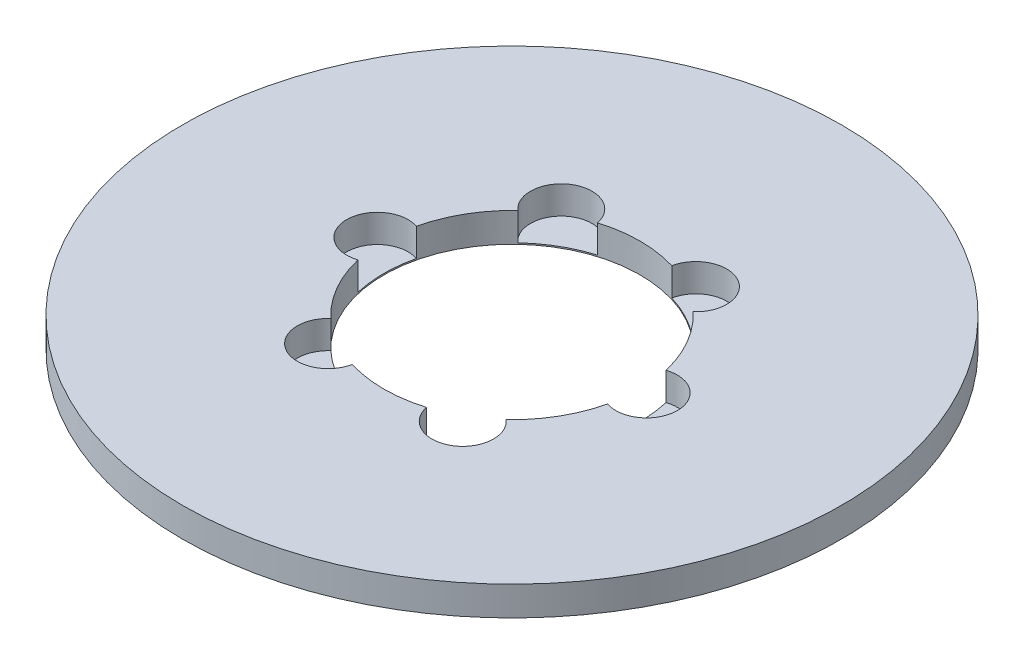
SolidWorks part; units mm, degrees
ref_plane "Front Plane" through (0, 0, 0) normal (0, 0, 1) x (1, 0, 0)
ref_plane "Top Plane" through (0, 0, 0) normal (0, 1, 0) x (1, 0, 0)
ref_plane "Right Plane" through (0, 0, 0) normal (1, 0, 0) x (0, 0, -1)
sketch "Sketch1" plane through (0, 0, 0) normal (0, 1, 0) x (1, 0, 0)
  circle A0 centre (0, 0) radius 45
  dimension "FLANGE_OD" = 90
extrude "Boss-Extrude1" add sketch "Sketch1" along normal blind 4
sketch "Sketch2" plane through (0, 0, 0) normal (0, 1, 0) x (1, 0, 0)
  circle A0 centre (0, 0) radius 17.5
  dimension "BORE_D" = 35
extrude "Cut-Extrude1" cut sketch "Sketch2" along normal through all
sketch "Sketch3" plane through (0, 4, 0) normal (0, 1, 0) x (1, 0, 0)
  circle A0 centre (0, 0) radius 18.3811 construction
  circle A1 centre (-18.3811, 0) radius 4.202
  dimension "BOLT_D" = 8.4039
  dimension "BOLT_PCD" = 36.7621
extrude "Cut-Extrude2" cut sketch "Sketch3" against normal blind 3.8183
pattern_circular "CirPattern1" count 6 over 360 about axis through (0, 0, 0) along (0, 1, 0) of "Cut-Extrude2"
